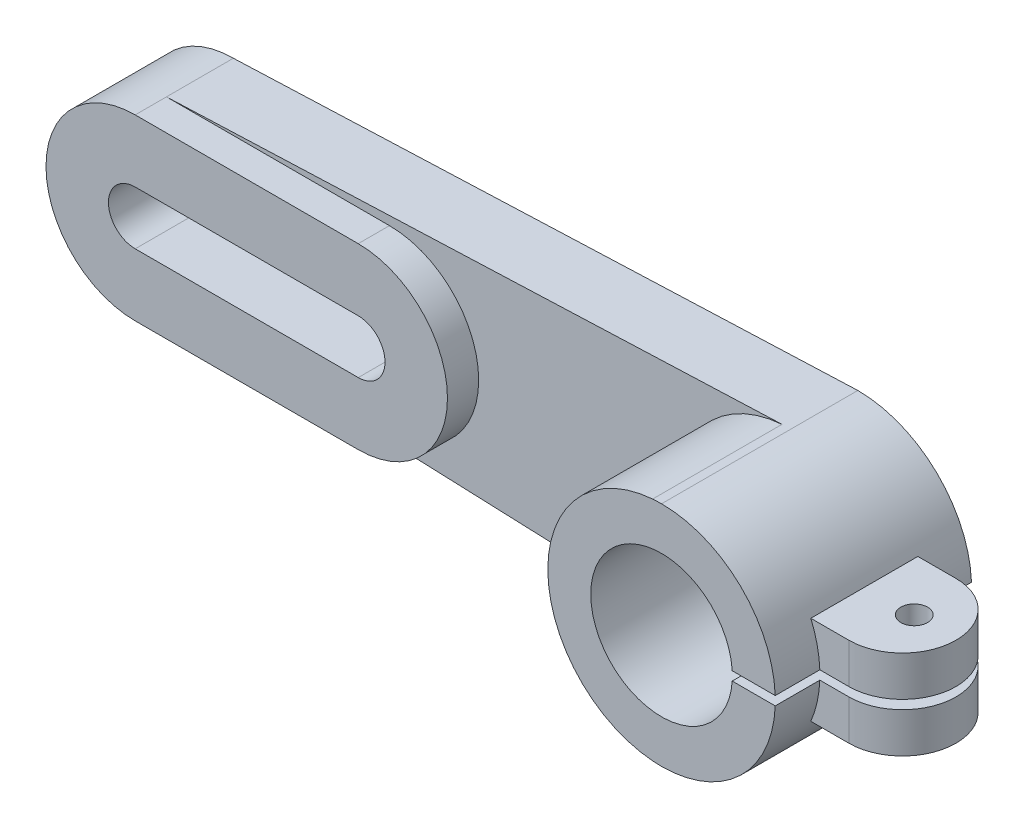
SolidWorks part; units mm, degrees
material "Chrome Stainless Steel"
ref_plane "Front Plane" through (0, 0, 0) normal (0, 0, 1) x (1, 0, 0)
ref_plane "Top Plane" through (0, 0, 0) normal (0, 1, 0) x (1, 0, 0)
ref_plane "Right Plane" through (0, 0, 0) normal (1, 0, 0) x (0, 0, -1)
sketch "Sketch1" plane through (0, 0, 0) normal (0, 0, 1) x (1, 0, 0)
  line L0 (0, 0) -> (23396.273, 0) construction
  line L1 (0, 0) -> (0, 23396.273) construction
  line L2 (-140, 0) -> (-90, 0) construction
  line L3 (-140, 20) -> (-90, 20)
  line L4 (-140, -20) -> (-90, -20)
  line L5 (-140, 0) -> (-90, 0) construction
  line L6 (-140, 6) -> (-90, 6)
  line L7 (-140, -6) -> (-90, -6)
  line L8 (0, 25.5) -> (-140, 20)
  line L9 (0, -25.5) -> (-140, -20)
  line L10 (15.8385, 1) -> (44, 1)
  line L11 (44, 1) -> (44, 10)
  line L12 (44, 10) -> (23.4574, 10)
  line L13 (44, -10) -> (23.4574, -10)
  line L14 (44, -1) -> (44, -10)
  line L15 (15.8385, -1) -> (44, -1)
  arc A0 (15.8385, 1) -> (15.8385, -1) centre (0, 0) ccw
  circle A1 centre (0, 0) radius 25.5
  arc A2 (-140, 20) -> (-140, -20) centre (-140, 0) ccw
  arc A3 (-90, -20) -> (-90, 20) centre (-90, 0) ccw
  arc A4 (-140, 6) -> (-140, -6) centre (-140, 0) ccw
  arc A5 (-90, -6) -> (-90, 6) centre (-90, 0) ccw
  point P10 (-115, 0)
  point P15 (-115, 0)
  dimension "D1" = 51
  dimension "D2" = 31.74
  dimension "D4" = 6
  dimension "D5" = 20
  dimension "D3" = 50
  dimension "D6" = 140
  dimension "D7" = 20
  dimension "D8" = 9
  dimension "D9" = 44
extrude "Boss-Extrude1" add sketch "Sketch1" along normal blind 44 contours L10 A1 L8 L9 L15 A0 region at (-0.9719, 24.7402, 0)
extrude "Boss-Extrude2" add sketch "Sketch1<3>" along normal blind 15 contours A3 L4 L9 A1 L8 L3 region at (-49.8705, 0, 0)
sketch "Sketch1<3>" plane through (0, 0, 0) normal (0, 0, 1) x (1, 0, 0) same geometry as "Sketch1"
extrude "Boss-Extrude3" add sketch "Sketch1<4>" along normal blind 22 contours L4 A3 L3 A2 A5 L7 A4 L6 region at (-115, 19.0151, 0)
sketch "Sketch1<4>" plane through (0, 0, 0) normal (0, 0, 1) x (1, 0, 0) same geometry as "Sketch1"
extrude "Boss-Extrude4" add sketch "Sketch1<5>" along normal blind 24 from offset 10 contours A1 L10 L11 L12 | A1 L13 L14 L15 region at (34.3692, 5.5783, 0) region at (34.3692, -5.5783, 0)
sketch "Sketch1<5>" plane through (0, 0, 0) normal (0, 0, 1) x (1, 0, 0) same geometry as "Sketch1"
fillet "Fillet3" 2 edges at (44, 5.5, 34) (44, 5.5, 10) type full round first side face at (34.337, 5.5231, 34) second side face at (34.337, 5.5231, 10) middle face at (44, 5.5, 22)
fillet "Fillet4" 2 edges at (44, -5.5, 34) (44, -5.5, 10) type full round first side face at (34.337, -5.5231, 34) second side face at (34.337, -5.5231, 10) middle face at (44, -5.5, 22)
hole_wizard "Ø6.0mm Dowel Hole1" positions "3DSketch1" profile "Sketch2" hole size "Ø6.0" standard "ISO" end condition through all
sketch3d "3DSketch1"
  point P0 (34.3879, 10, 21.7469)
sketch "Sketch2" plane through (34.3879, 10, 21.7469) normal (1, 0, 0) x (0, 0, 1)
  line L0 (0, 0) -> (0, 35.5)
  line L1 (0, 35.5) -> (3, 35.5)
  line L2 (3, 35.5) -> (3, 0)
  line L5 (3, 0) -> (0, 0)
  line L11 (0, -6.35) -> (0, 107.95) construction
  dimension "Thru Hole Dia." = 6
  dimension "Thru Hole Depth" = 35.5
